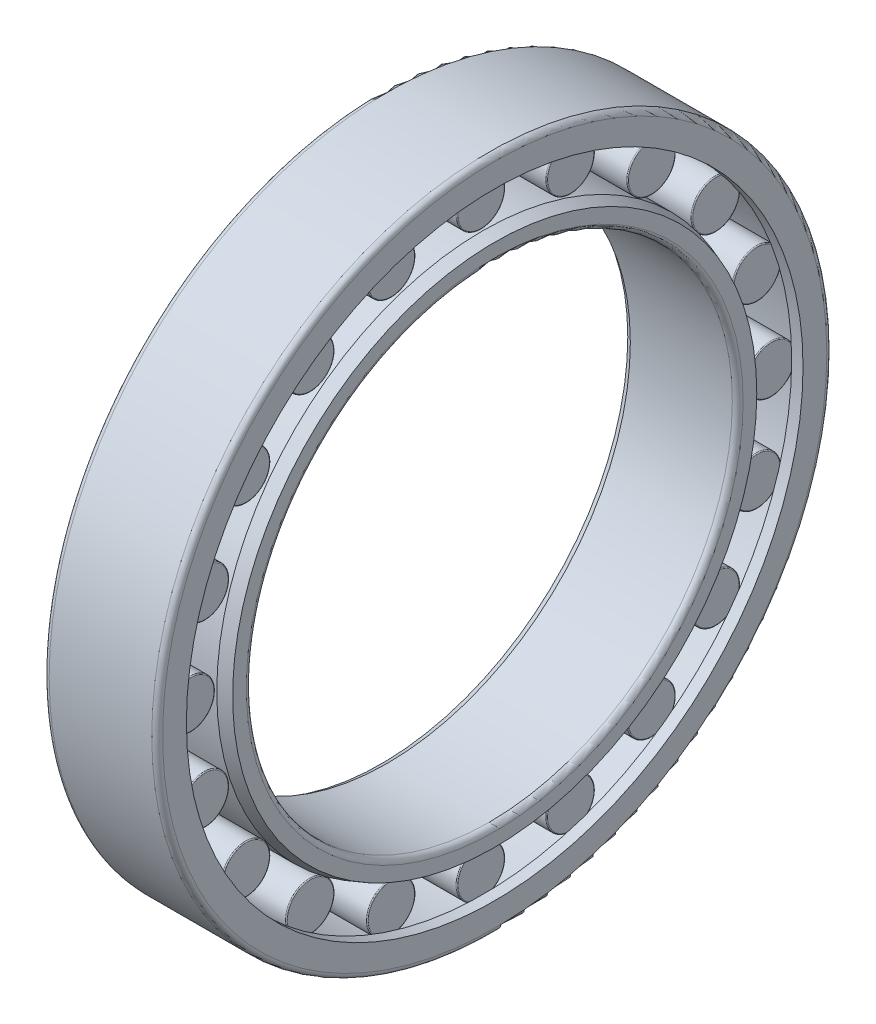
SolidWorks part; units mm, degrees
ref_plane "Plane1" through (0, 0, 0) normal (0, 0, 1) x (1, 0, 0)
ref_plane "Plane2" through (0, 0, 0) normal (0, 1, 0) x (1, 0, 0)
ref_plane "Plane3" through (0, 0, 0) normal (1, 0, 0) x (0, 0, -1)
sketch "Clipboard" plane through (0, 0, 0) normal (0, 0, 1) x (1, 0, 0)
  line L0 (-10, 0) -> (10, 0) construction
  line L1 (0, 0) -> (185.2698, -67.4327)
  line L2 (0, 0) -> (101.017, 36.7672)
  line L3 (0, 0) -> (218.798, -79.636)
  line L4 (0, 0) -> (-22.3471, -0.7804)
  dimension "Race_OD" = 232.84
  dimension "Race_ID" = 197.16
sketch "OutRacSke" plane through (0, 0, 0) normal (0, 0, 1) x (1, 0, 0)
  line L0 (-16.8, 114.1887) -> (-21, 114.1887)
  line L1 (-21, 114.1887) -> (-21, 123)
  line L2 (-19, 125) -> (19, 125)
  line L3 (21, 123) -> (21, 114.1888)
  line L4 (21, 114.1888) -> (16.8, 114.1888)
  line L5 (16.8, 114.1888) -> (16.8, 116.42)
  line L6 (16.8, 116.42) -> (-16.8, 116.42)
  line L7 (-16.8, 116.42) -> (-16.8, 114.1887)
  line L8 (-90, 0) -> (90, 0) construction
  arc A0 (-21, 123) -> (-19, 125) centre (-19, 123) cw
  arc A1 (19, 125) -> (21, 123) centre (19, 123) cw
  dimension "Race_OD" = 232.84
  dimension "radius" = 2
  dimension "halfWidth" = 21
  dimension "groove_dp" = 2.2313
  dimension "Cyl_Len" = 33.6
revolve "OuterRace" add sketch "OutRacSke" angle 360 about L8 reverse direction yes
sketch "RolDetSke" plane through (0, 0, 0) normal (0, 0, 1) x (1, 0, 0)
  line L0 (-15.96, 116.068) -> (-15.96, 107.5)
  line L1 (-15.96, 107.5) -> (15.96, 107.5)
  line L2 (15.96, 107.5) -> (15.96, 116.068)
  line L3 (15.603, 116.425) -> (-15.603, 116.425)
  line L4 (-33.6, 107.5) -> (33.6, 107.5) construction
  arc A0 (15.96, 116.068) -> (15.603, 116.425) centre (15.603, 116.068) ccw
  arc A1 (-15.603, 116.425) -> (-15.96, 116.068) centre (-15.603, 116.068) ccw
  dimension "radius" = 0.357
  dimension "Roller_diameter" = 17.85
  dimension "halfLength" = 15.96
revolve "RollerDetailed" add sketch "RolDetSke" angle 360 about L4 reverse direction yes
ref_axis "Axis1" through (-50, 0, 0) along (1, 0, 0)
sketch "RolSimSke" plane through (0, 101.6, 0) normal (0, 0, 1) x (1, 0, 0)
  line L0 (-15.96, 14.468) -> (-15.96, -2.668)
  line L1 (25.4, -101.6) -> (-25.4, -101.6) construction
  line L2 (15.96, -2.668) -> (15.96, 14.468)
  line L3 (15.603, 14.825) -> (-15.603, 14.825)
  line L5 (15.603, -3.025) -> (-15.603, -3.025)
  arc A0 (15.96, 14.468) -> (15.603, 14.825) centre (15.603, 14.468) ccw
  arc A1 (-15.603, 14.825) -> (-15.96, 14.468) centre (-15.603, 14.468) ccw
  arc A2 (15.96, -2.668) -> (15.603, -3.025) centre (15.603, -2.668) cw
  arc A3 (-15.603, -3.025) -> (-15.96, -2.668) centre (-15.603, -2.668) cw
  dimension "radius" = 0.357
  dimension "D1" = 98.575
  dimension "Roller_diameter" = 17.85
  dimension "halfLength" = 15.96
revolve "RollersSimplified" [suppressed] add sketch "RolSimSke" angle 360 about L1
sketch "InsRacSke" plane through (0, 0, 0) normal (0, 0, 1) x (1, 0, 0)
  line L0 (-16.9589, 98.58) -> (-21, 96.3487)
  line L1 (-21, 96.3487) -> (-21, 91.2882)
  line L2 (-18.7687, 90) -> (19, 90)
  line L3 (21, 92) -> (21, 97.0605)
  line L4 (21, 97.0605) -> (16.6411, 98.58)
  line L5 (16.6411, 98.58) -> (-16.9589, 98.58)
  line L6 (-90, 0) -> (90, 0) construction
  line L7 (-21, 91.2882) -> (-18.7687, 90)
  arc A1 (19, 90) -> (21, 92) centre (19, 92) ccw
  point P14 (-21, 90)
  dimension "radius" = 2
  dimension "Race_ID" = 197.16
  dimension "Width" = 42
  dimension "halfWidth" = 21
  dimension "groove_dp" = 2.2313
  dimension "Cyl_Len" = 33.6
  dimension "D2" = 30
revolve "InnerRace" add sketch "InsRacSke" angle 360 about L6 reverse direction yes
pattern_circular "RollersDetailed" count 20 every 18 about axis through (-50, 0, 0) along (1, 0, 0) of "RollerDetailed"
sketch "CagSpiSke" plane through (0, 0, 0) normal (0, 0, 1) x (1, 0, 0)
  line L0 (-18.9, 109.7313) -> (-12.6, 109.7313)
  line L1 (18.9, 109.7313) -> (12.6, 109.7313)
  line L2 (-12.6, 109.7313) -> (-6.3, 105.2687)
  line L3 (-6.3, 105.2687) -> (6.3, 105.2687)
  line L4 (-90, 0) -> (90, 0) construction
  line L5 (12.6, 109.7313) -> (6.3, 105.2687)
  line L6 (0, 0) -> (0, 33.2193) construction
  dimension "width" = 37.8
  dimension "offset" = 6.3
revolve "CageSpine" [suppressed] add sketch "CagSpiSke" angle 360 about L4 wall 1
equation "\"CLdia@Clipboard\" =  ( \"Race_OD@Clipboard\" + \"Race_ID@Clipboard\" )  / 4"
equation "\"Race_OD@OutRacSke\" = \"Race_OD@Clipboard\""
equation "\"halfCylLen@OutRacSke\" = \"Cyl_Len@OutRacSke\" / 2"
equation "\"RolCLRad@RolDetSke\" = \"CLdia@Clipboard\""
equation "\"Roller_diameter@RolDetSke\" =  ( \"Race_OD@Clipboard\" - \"Race_ID@Clipboard\" )  / 2 + .01"
equation "\"Roller_diameter@RolSimSke\" =  ( \"Race_OD@Clipboard\" - \"Race_ID@Clipboard\" )  / 2 + .01"
equation "\"radius@RolDetSke\" = \"Roller_diameter@RolDetSke\" / 50"
equation "\"Length@RolDetSke\" = \"Cyl_Len@OutRacSke\" * .95"
equation "\"halfLength@RolDetSke\" = \"Length@RolDetSke\" / 2"
equation "\"thickness@CagSpiSke\"  = \"Roller_diameter@RolDetSke\" * .25"
equation "\"Cag_IR@CagSpiSke\" =  \"RolCLRad@RolDetSke\" * 2 - \"thickness@CagSpiSke\""
equation "\"Rol_Length@RolSimSke\" = \"Cyl_Len@InsRacSke\" * .95"
equation "\"halfLength@RolSimSke\" = \"Rol_Length@RolSimSke\" / 2"
equation "\"radius@RolSimSke\" = \"radius@RolDetSke\""
equation "\"D1@RolSimSke\" = \"CLdia@Clipboard\" -  ( \"Roller_diameter@RolSimSke\" / 2 ) "
equation "\"Max_count@Clipboard\" = int( 3.14159265 / atn(( \"Roller_diameter@RolDetSke\" / 2) / sqr( \"RolCLRad@RolDetSke\"  *  \"RolCLRad@RolDetSke\" - ( \"Roller_diameter@RolDetSke\" / 2) *  ( \"Roller_diameter@RolDetSke\" / 2))))"
equation "\"Max_count@Clipboard\" = ((sgn( \"Max_count@Clipboard\" - \"Count@Clipboard\" )-1)*( \"Max_count@Clipboard\" - \"Count@Clipboard\" ))/-2+ \"Count@Clipboard\""
equation "\"Count@RollersDetailed\" = int( \"Show_count@Clipboard\" ) "
equation "\"Count@RollersDetailed\" = ((sgn( \"Count@RollersDetailed\" - \"Max_count@Clipboard\" )-1)*( \"Count@RollersDetailed\" - \"Max_count@Clipboard\" ))/-2+ \"Max_count@Clipboard\""
equation "\"Count@RollersDetailed\" = ((sgn( \"Count@RollersDetailed\" - \"Min_count@Clipboard\" )+1)*( \"Count@RollersDetailed\" - \"Min_count@Clipboard\"))/2 +\"Min_count@Clipboard\""
equation "\"Angle@RollersDetailed\" = 360.0 / \"Max_count@Clipboard\""
equation "\"radius@InsRacSke\" = \"radius@OutRacSke\""
equation "\"groove_dp@InsRacSke\" = \"groove_dp@OutRacSke\""
equation "\"chamfer@InsRacSke\" = \"groove_dp@InsRacSke\""
equation "\"Width@InsRacSke\" = \"Width@OutRacSke\""
equation "\"halfWidth@OutRacSke\" = \"Width@OutRacSke\" / 2"
equation "\"halfWidth@InsRacSke\" = \"Width@InsRacSke\" / 2"
equation "\"Race_ID@InsRacSke\" = \"Race_ID@Clipboard\""
equation "\"Cyl_Len@InsRacSke\" = \"Cyl_Len@OutRacSke\""
equation "\"Angle@CageSpine\" =  \"Angle@RollersDetailed\" * ( \"Count@RollersDetailed\" -1 + int( \"Count@RollersDetailed\" / \"Max_count@Clipboard\" ) )  + 0.001 -  int( \"Count@RollersDetailed\" / \"Max_count@Clipboard\" ) * 0.001"
equation "\"Angle@CageSpine\" =  \"Angle@CageSpine\" * int( \"Min_count@Clipboard\" / 2) + int(1 / \"Min_count@Clipboard\")  * 0.001"
equation "\"width@CagSpiSke\" =   ( \"Width@InsRacSke\" + \"Cyl_Len@InsRacSke\" )  / 2"
equation "\"step_width@CagSpiSke\" = \"width@CagSpiSke\" / 6"
equation "\"offset@CagSpiSke\" = \"step_width@CagSpiSke\""
